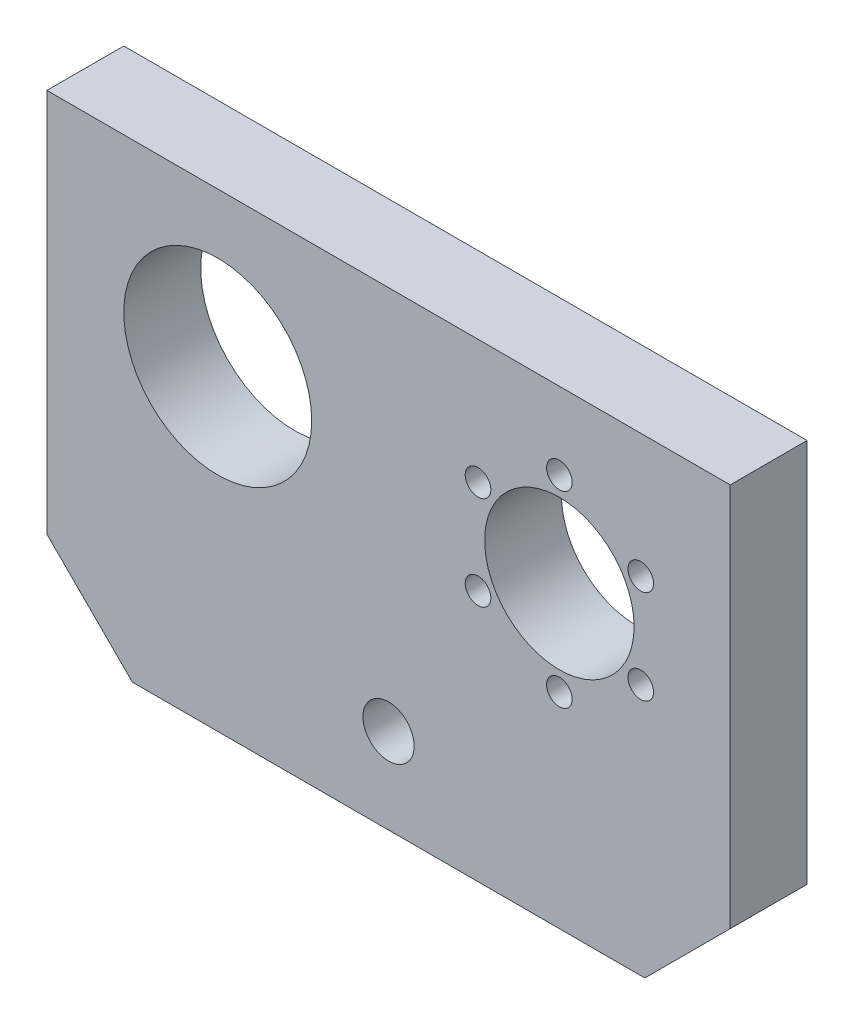
SolidWorks part; units mm, degrees
ref_plane "Front" through (0, 0, 0) normal (0, 0, 1) x (1, 0, 0)
ref_plane "Top" through (0, 0, 0) normal (0, 1, 0) x (1, 0, 0)
ref_plane "Right" through (0, 0, 0) normal (1, 0, 0) x (0, 0, -1)
sketch "Esquisse1" plane through (0, 0, 0) normal (0, 0, 1) x (1, 0, 0)
  line L1 (0, 0) -> (80, 0)
  line L2 (0, 0) -> (0, 55)
  line L3 (0, 55) -> (80, 55)
  line L4 (80, 0) -> (80, 55)
  dimension "D1" = 55
  dimension "D2" = 80
extrude "Boss.-Extru.1" add sketch "Esquisse1" along normal blind 9
sketch "Esquisse2" plane through (0, 0, 9) normal (0, 0, 1) x (1, 0, 0)
  line L0 (20, 55) -> (20, 0) construction
  line L1 (80, 55) -> (0, 55) construction
  line L2 (0, 0) -> (80, 0) construction
  line L4 (60, 35) -> (60, 55) construction
  line L6 (0, 55) -> (0, 0) construction
  circle A0 centre (20, 37) radius 11
  circle A1 centre (60, 35) radius 8.75
  circle A2 centre (60, 46) radius 1.5
  circle A3 centre (69.5263, 40.5) radius 1.5
  circle A4 centre (69.5263, 29.5) radius 1.5
  circle A5 centre (60, 24) radius 1.5
  circle A6 centre (50.4737, 29.5) radius 1.5
  circle A7 centre (50.4737, 40.5) radius 1.5
  point P8 (70.2258, 55)
  point P9 (16.2023, 55)
  point P29 (60, 35)
  dimension "D1" = 22
  dimension "D2" = 18
  dimension "D4" = 17.5
  dimension "D7" = 3
  dimension "D3" = 20
  dimension "D5" = 20
  dimension "D6" = 20
  dimension "D8" = 11
  dimension "D9" = 6
extrude "Enlèv. mat.-Extru.1" cut sketch "Esquisse2" against normal through all
sketch "Esquisse3" plane through (0, 0, 9) normal (0, 0, 1) x (1, 0, 0)
  circle A0 centre (40, 10) radius 3
  circle A1 centre (60, 35) radius 8.75 construction
  point P4 (40.5864, 10)
  dimension "D3" = 6
  dimension "D1" = 25
  dimension "D2" = 20
extrude "Enlèv. mat.-Extru.2" cut sketch "Esquisse3" against normal through all
chamfer "Chanfrein1" distance 10 angle 45 2 edges at (80, 0, 4.5) (0, 0, 4.5)
